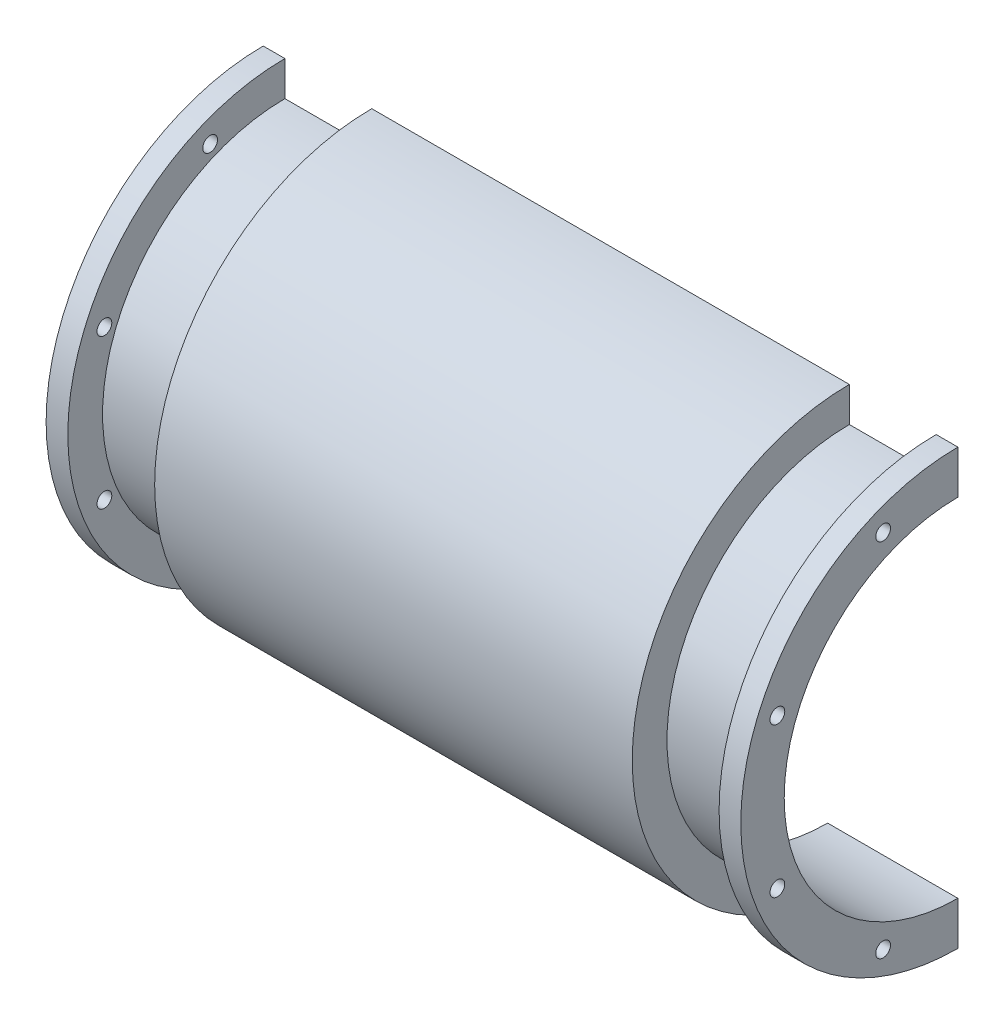
SolidWorks part; units mm, degrees
ref_plane "正面" through (0, 0, 0) normal (0, 0, 1) x (1, 0, 0)
ref_plane "平面" through (0, 0, 0) normal (0, 1, 0) x (1, 0, 0)
ref_plane "右側面" through (0, 0, 0) normal (1, 0, 0) x (0, 0, -1)
sketch "ｽｹｯﾁ1" plane through (0, 0, 0) normal (0, 0, 1) x (1, 0, 0)
  line L0 (-80, 40) -> (-50, 40)
  line L1 (-50, 40) -> (-50, 49)
  line L2 (-50, 49) -> (50, 49)
  line L3 (50, 49) -> (50, 40)
  line L4 (50, 40) -> (80, 40)
  line L5 (80, 40) -> (80, 50)
  line L6 (80, 50) -> (75, 50)
  line L7 (75, 50) -> (75, 42)
  line L8 (75, 42) -> (55, 42)
  line L9 (55, 42) -> (55, 50)
  line L10 (55, 50) -> (-55, 50)
  line L11 (-55, 50) -> (-55, 42)
  line L12 (-55, 42) -> (-75, 42)
  line L13 (-75, 42) -> (-75, 50)
  line L14 (-75, 50) -> (-80, 50)
  line L15 (-80, 50) -> (-80, 40)
  point P3 (0, 49)
  point P18 (0, 50)
  dimension "D1" = 1
  dimension "D2" = 10
  dimension "D3" = 2
  dimension "D4" = 160
  dimension "D5" = 5
  dimension "D6" = 5
  dimension "D7" = 20
  dimension "D8" = 50
sketch "ｽｹｯﾁ2" plane through (0, 0, 0) normal (0, 0, 1) x (1, 0, 0)
  line L0 (-50, 0) -> (50, 0)
  point P3 (0, 0)
  dimension "D1" = 100
revolve "回転1" add sketch "ｽｹｯﾁ1" angle 180 about L0
hole_wizard "M3 すきま穴1" positions "ｽｹｯﾁ5" profile "ｽｹｯﾁ6" hole size "M3" standard "JIS" end condition up to next
sketch "ｽｹｯﾁ5" plane through (-80, 0, 0) normal (-1, 0, 0) x (0, 0, 1)
  line L5 (0, 0) -> (17.2208, -41.5746)
  line L7 (0, -50) -> (0, -40) construction
  circle A0 centre (0, 0) radius 40 construction
  point P0 (17.2208, -41.5746)
  dimension "D1" = 45
  dimension "D2" = 22.5
sketch "ｽｹｯﾁ6" plane through (-80, -41.5746, 17.2208) normal (0, 1, 0) x (0, 0, 1)
  line L0 (0, 0) -> (0, 5)
  line L1 (0, 5) -> (1.7, 5)
  line L2 (1.7, 5) -> (1.7, 0)
  line L5 (1.7, 0) -> (0, 0)
  line L11 (0, -6.35) -> (0, 107.95) construction
  dimension "通し穴の直径" = 3.4
  dimension "通し穴の深さ" = 5
pattern_circular "円形ﾊﾟﾀｰﾝ1" count 4 every 45 about axis through (-80, 0, 0) along (-1, 0, 0) of "M3 すきま穴1"
mirror "ﾐﾗｰ1" about plane through (0, 0, 0) normal (1, 0, 0) of "円形ﾊﾟﾀｰﾝ1"
fillet "ﾌｨﾚｯﾄ1" radius 9 2 edges at (-50, 0, 49) (50, 0, 49)
